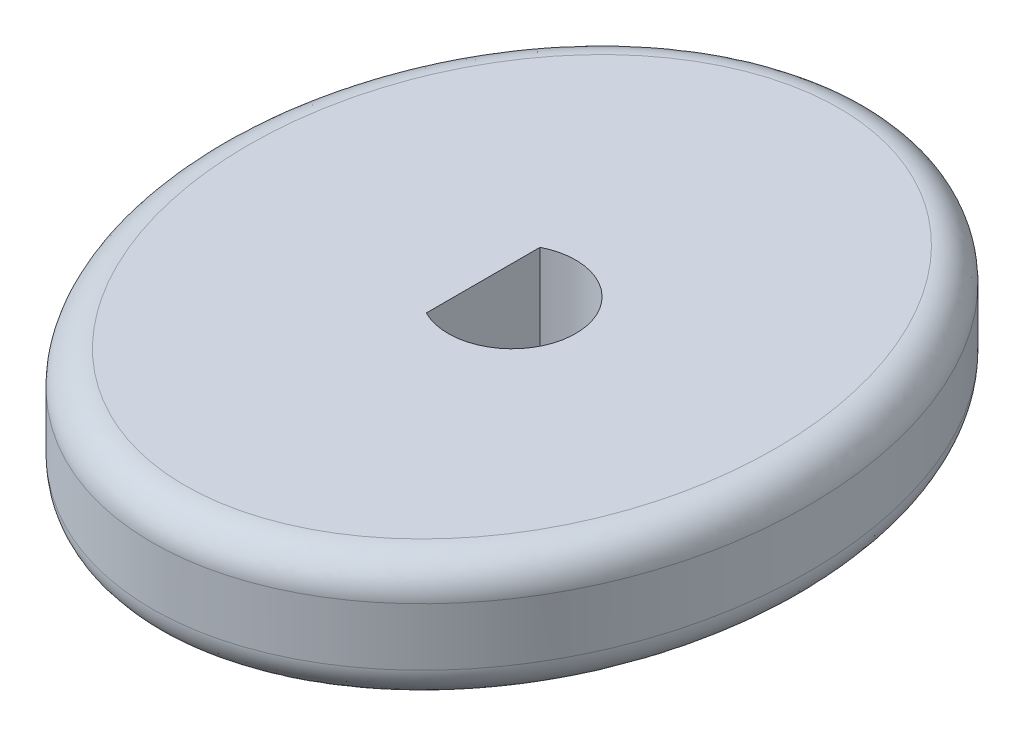
SolidWorks part; units mm, degrees
ref_plane "Front Plane" through (0, 0, 0) normal (0, 0, 1) x (1, 0, 0)
ref_plane "Top Plane" through (0, 0, 0) normal (0, 1, 0) x (1, 0, 0)
ref_plane "Right Plane" through (0, 0, 0) normal (1, 0, 0) x (0, 0, -1)
sketch "Sketch1" plane through (0, 0, 0) normal (0, 1, 0) x (1, 0, 0)
  line L0 (-7.2, 0) -> (7.2, 0) construction
  line L1 (-0.7, 1.3829) -> (-0.7, -1.3829)
  arc A6 (-0.7, -1.3829) -> (-0.7, 1.3829) centre (0, 0) ccw
  ellipse E0 centre (0, 0) end of major axis (0, 8.75) minor radius 7.2
  dimension "D1" = 3.1
  dimension "D2" = 0.7
  dimension "D3" = 17.5
  dimension "12" = 14.4
extrude "Boss-Extrude1" add sketch "Sketch1" along normal blind 1.5 and the other way blind 1.5
fillet "Fillet1" radius 0.8 2 edges at (0, -1.5, -8.75) (0, 1.5, -8.75)
